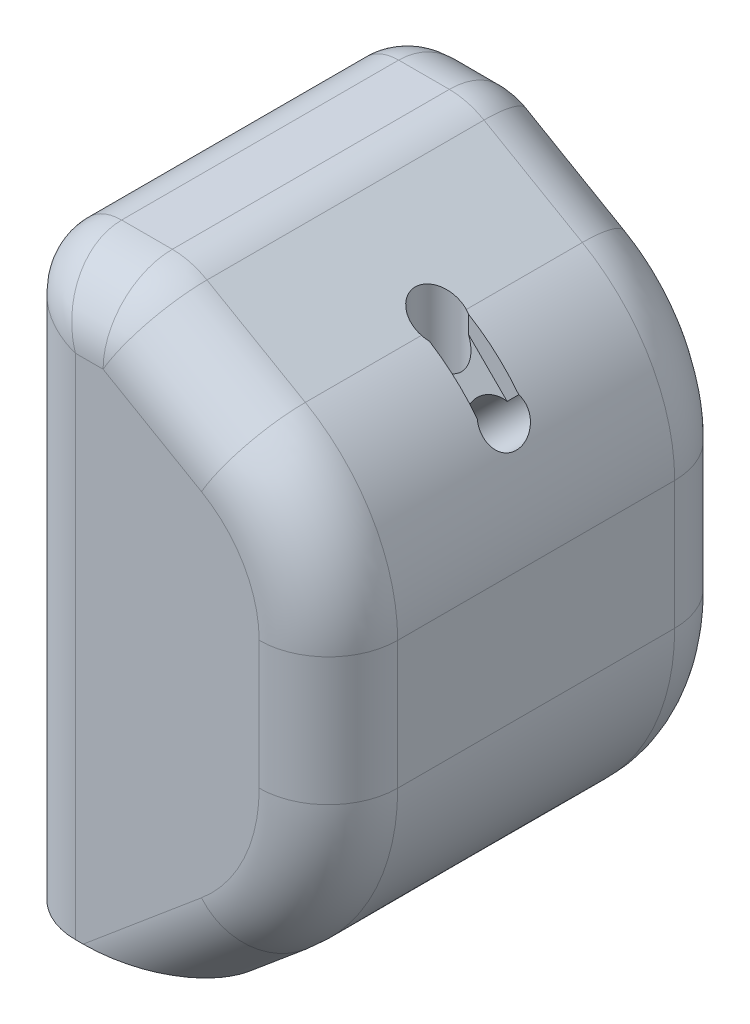
SolidWorks part; units mm, degrees
ref_plane "Front Plane" through (0, 0, 0) normal (0, 0, 1) x (1, 0, 0)
ref_plane "Top Plane" through (0, 0, 0) normal (0, 1, 0) x (1, 0, 0)
ref_plane "Right Plane" through (0, 0, 0) normal (1, 0, 0) x (0, 0, -1)
sketch "Sketch1" plane through (0, 0, 0) normal (0, 0, 1) x (1, 0, 0)
  line L0 (0, 0) -> (8, 0)
  line L1 (8, 0) -> (10.3866, 2.0026)
  line L2 (0, 0) -> (0, 23)
  line L3 (2, 25) -> (4.1962, 25)
  line L4 (5.6962, 24.5981) -> (9.9588, 22.1371)
  line L5 (13.9588, 15.2089) -> (13.9588, 9.6631)
  arc A0 (0, 23) -> (2, 25) centre (2, 23) cw
  arc A1 (5.6962, 24.5981) -> (4.1962, 25) centre (4.1962, 22) ccw
  arc A2 (13.9588, 15.2089) -> (9.9588, 22.1371) centre (5.9588, 15.2089) ccw
  arc A3 (13.9588, 9.6631) -> (10.3866, 2.0026) centre (3.9588, 9.6631) cw
  point P9 (0, 25)
  point P12 (5, 25)
  point P15 (13.9588, 19.8277)
  point P18 (13.9588, 5)
  dimension "D7" = 2
  dimension "D8" = 3
  dimension "D9" = 8
  dimension "D10" = 10
  dimension "D1" = 8
  dimension "D2" = 140
  dimension "D3" = 5
  dimension "D4" = 25
  dimension "D5" = 5
  dimension "D6" = 150
extrude "Boss-Extrude1" add sketch "Sketch1" along normal blind 18
sketch "Sketch2" plane through (0, 0, 0) normal (0, 0, -1) x (-1, 0, 0)
  line L0 (0, 0) -> (-8, 0) construction
  line L2 (-6, 0) -> (-4, 0)
  line L3 (-6, 0) -> (-6, 1.2087)
  line L5 (-4, 0) -> (-4, 1.2087)
  arc A0 (-4, 1.2087) -> (-6, 1.2087) centre (-5, 3.5) ccw
  point P0 (-5, 0)
  dimension "D2" = 5
  dimension "D1" = 5
  dimension "D3" = 3.5
  dimension "D4" = 2
  dimension "D5" = 1
extrude "Cut-Extrude1" cut sketch "Sketch2" against normal blind 13 from offset 2.5 offset against normal yes
sketch "Sketch4" plane through (0, 0, 0) normal (0, 1, 0) x (1, 0, 0)
  circle A0 centre (9.7202, -9) radius 1
  point P2 (0, 0)
  point P3 (0, 0)
  dimension "D1" = 2
  dimension "D2" = 9.7202
  dimension "D3" = 9
extrude "Cut-Extrude3" cut sketch "Sketch4" along normal blind 25
ref_plane "Plane1" through (16.0479, 16.0479, 0) normal (0.7071, 0.7071, 0) x (0, 0, -1)
sketch "Sketch5" plane through (16.0479, 16.0479, 0) normal (0.7071, 0.7071, 0) x (0, 0, -1)
  circle A0 centre (-8.9711, 5.1113) radius 1
  point P0 (-8.9711, 8.6113)
  dimension "D1" = 2
  dimension "D2" = 3.5
  dimension "D3" = 1
extrude "Cut-Extrude4" cut sketch "Sketch5" against normal blind 4 and the other way blind 2
fillet "Fillet1" radius 3 18 edges at (9.1933, 1.0013, 0) (13.0218, 5.4369, 0) (13.9588, 12.436, 0) (12.887, 19.2089, 0) (7.8275, 23.3676, 0) (4.9726, 24.8978, 0) (3.0981, 25, 0) (0.5858, 24.4142, 0) (9.1933, 1.0013, 18) (13.0218, 5.4369, 18) (13.9588, 12.436, 18) (12.887, 19.2089, 18) (7.8275, 23.3676, 18) (4.9726, 24.8978, 18) (3.0981, 25, 18) (0.5858, 24.4142, 18) (0, 11.5, 0) (0, 11.5, 18)
sketch "Sketch6" plane through (16.0479, 16.0479, 0) normal (0.7071, 0.7071, 0) x (0, 0, -1)
  line L1 (-9.8711, 5.1113) -> (-8.0711, 5.1113)
  line L2 (-9.8711, 5.1113) -> (-9.8711, 8.8774)
  line L3 (-9.8711, 8.8774) -> (-8.0711, 8.8774)
  line L4 (-8.0711, 5.1113) -> (-8.0711, 8.8774)
  circle A0 centre (-8.9711, 5.1113) radius 1 construction
  ellipse E0 centre (-9, 8.8774) end of major axis (-9, 7.762) minor radius 1 (-8.0289, 8.6113) -> (-9.9711, 8.6113) ccw construction
  ellipse E1 centre (-9, 8.8774) end of major axis (-9, 7.762) minor radius 1 (-8.0289, 8.6113) -> (-9.9711, 8.6113) ccw construction
  point P5 (-9.5485, 4.2949)
  point P10 (-8.9711, 5.1113)
  dimension "D1" = 1.8
  dimension "D2" = 0.9
  dimension "D3" = 0.1289
extrude "Cut-Extrude5" cut sketch "Sketch6" along normal blind 1 and the other way blind 0.5
sketch "Sketch7" plane through (0, 0, 0) normal (-1, 0, 0) x (0, 0, 1)
  line L0 (2.9999, 14.4276) -> (3, 13)
  line L1 (3, 23) -> (3, 0) construction
  line L2 (3, 13) -> (15, 13)
  line L3 (15, 0) -> (15, 23) construction
  line L4 (15, 13) -> (15, 14.4276)
  line L5 (15, 23) -> (3, 23) construction
  spline S0 degree 3 poles (2.9999, 14.4276) (2.3845, 21.2849) (9.084, 24.4107) (15.4091, 21.3672) (15, 14.4276) knots 0 0 0 0 0.49958 1 1 1 1
  dimension "D1" = 10
extrude "Cut-Extrude6" cut sketch "Sketch7" against normal blind 0.5
ref_plane "Plane2" through (0, 0, 9) normal (0, 0, 1) x (1, 0, 0)
